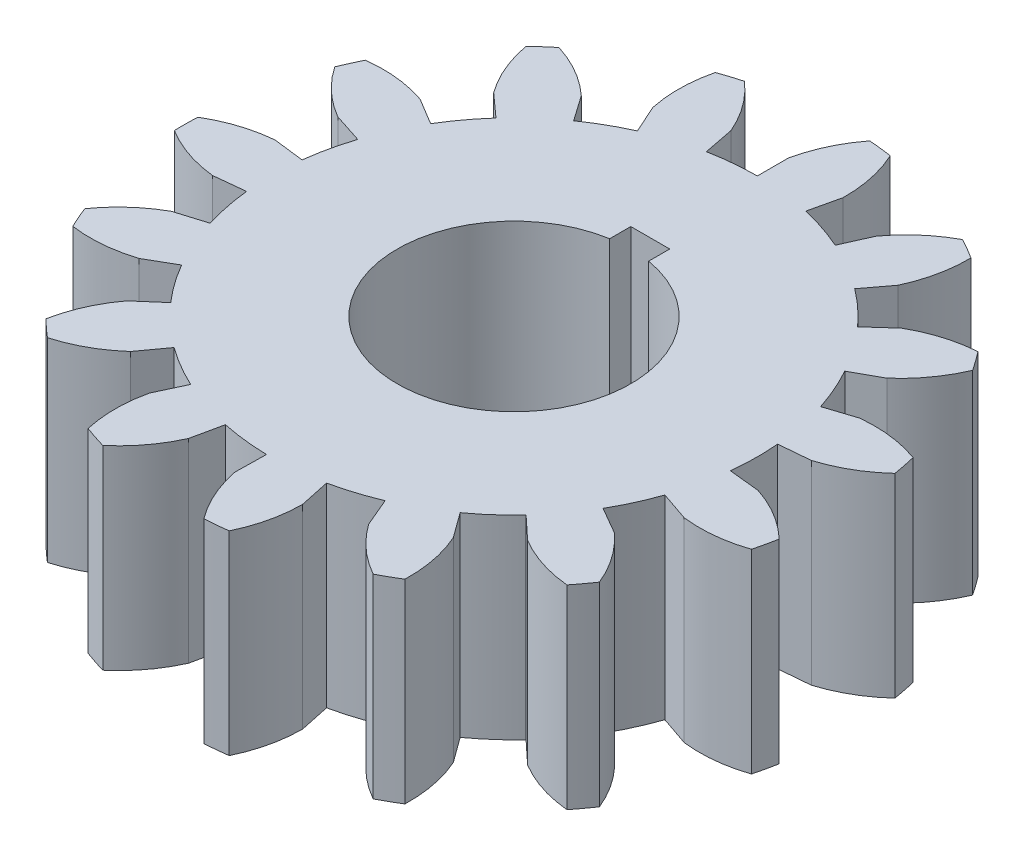
SolidWorks part; units mm, degrees
ref_plane "Front Plane" through (0, 0, 0) normal (0, 0, 1) x (1, 0, 0)
ref_plane "Top Plane" through (0, 0, 0) normal (0, 1, 0) x (1, 0, 0)
ref_plane "Right Plane" through (0, 0, 0) normal (1, 0, 0) x (0, 0, -1)
sketch "Sketch1" plane through (0, 0, 0) normal (0, 1, 0) x (1, 0, 0)
  circle A3 centre (0, 0) radius 6.25
  circle A4 centre (0, 0) radius 8.5
  circle A5 centre (0, 0) radius 7.5
  circle A6 centre (0, 0) radius 6.5
  circle A7 centre (0, 0) radius 7.0477
  dimension "pitch circle" = 15
  dimension "addendum circle" = 17
  dimension "root circle" = 12.5
  dimension "clearance circle" = 13
  dimension "base circle" = 14.0954
sketch "Sketch2" plane through (0, 0, 0) normal (0, 1, 0) x (1, 0, 0)
  line L0 (0, 0) -> (0, 7.0477)
  line L1 (0, 0) -> (3.5238, 6.1035) construction
  line L2 (0, 0) -> (6.1035, 3.5238) construction
  line L3 (0, 0) -> (7.0477, 0) construction
  line L4 (7.0477, 0) -> (7.0477, 11.0705) construction
  line L5 (6.1035, 3.5238) -> (2.4133, 9.9154) construction
  line L6 (3.5238, 6.1035) -> (0.3281, 7.9486) construction
  line L7 (0, 0) -> (3.0505, 6.8516)
  line L8 (0, 0) -> (1.5593, 7.3361) construction
  line L9 (0.8482, 7.4519) -> (0, 0) construction
  circle A0 centre (0, 0) radius 7.0477 construction
  circle A1 centre (0, 0) radius 7.5 construction
  arc A2 (1.5593, 7.3361) -> (0.1292, 7.4989) centre (0, 0) ccw
  spline S0 degree 3 poles (0, 7.0477) (0.62, 9.9338) (4.6694, 11.0743) (7.0477, 11.0705) knots 0 0 0 0 1 1 1 1
  spline S1 degree 3 poles (1.5838, 6.8674) (1.6283, 9.8191) (-2.0612, 11.8403) (-4.3795, 12.3712) knots 0 0 0 0 1 1 1 1
  point P11 (0, 0)
  point P21 (0, 0)
  point P22 (0, 0)
  point P23 (0, 0)
  point P24 (0, 0)
  point P25 (0, 0)
  point P26 (0, 0)
  dimension "Involute Control" = 90
  dimension "Base circle quarter circumference" = 11.0705
  dimension "D1" = 7.3803
  dimension "D2" = 3.6902
  dimension "pitch circle" = 24
  dimension "Involute array" = 4
sketch "Sketch3" plane through (0, 0, 0) normal (0, 1, 0) x (1, 0, 0)
  line L0 (1.5838, 6.8674) -> (1.4046, 6.0901)
  line L1 (0, 0) -> (0, 7.0477) construction
  line L3 (0, 6.25) -> (0, 7.0477)
  arc A1 (0.6639, 8.474) -> (0, 7.0477) centre (3.4619, 6.3041) ccw
  circle A2 centre (0, 0) radius 8.5 construction
  circle A3 centre (0, 0) radius 6.25 construction
  arc A7 (1.5838, 6.8674) -> (1.2575, 8.4065) centre (-1.9566, 6.9208) ccw
  arc A8 (1.4046, 6.0901) -> (0, 6.25) centre (0, 0) ccw
  arc A9 (1.2575, 8.4065) -> (0.6639, 8.474) centre (0, 0) ccw
  circle A10 centre (0, 0) radius 7.0477 construction
  spline S0 degree 3 poles (1.5838, 6.8674) (1.6283, 9.8191) (-2.0612, 11.8403) (-4.3795, 12.3712) knots 0 0 0 0 1 1 1 1 construction
  spline S1 degree 3 poles (0, 7.0477) (0.62, 9.9338) (4.6694, 11.0743) (7.0477, 11.0705) knots 0 0 0 0 1 1 1 1 construction
  point P5 (1.4736, 8.3713)
  point P6 (0, 0)
  point P15 (0.5842, 8.4799)
  point P16 (0, 0)
  point P22 (1.723, 6.0078)
  point P24 (1.3461, 6.1033)
  point P25 (0, 6.9566)
  point P28 (0.0787, 6.2495)
  point P29 (0, 0)
  point P32 (0, 0)
  point P33 (0, 0)
  point P34 (1.4046, 6.0901)
extrude "Boss-Extrude1" add sketch "Sketch3" along normal blind 5
sketch "Sketch5" plane through (0, 0, 0) normal (1, 0, 0) x (0, 0, -1)
  line L0 (0, 0) -> (0, 5.4709) construction
pattern_circular "CirPattern4" count 15 over 360 about axis through (0, 0, 0) along (0, 1, 0) reverse direction yes of bodies 101
sketch "Sketch6" plane through (0, 0, 0) normal (0, 1, 0) x (1, 0, 0)
  circle A0 centre (0, 0) radius 6.25 construction
  circle A1 centre (0, 0) radius 6.25
extrude "Boss-Extrude2" add sketch "Sketch6" along normal up to surface (5 mm away) up to face at (-2.1817, 5, -6.9167)
sketch "Sketch7" plane through (0, 5, 0) normal (0, 1, 0) x (1, 0, 0)
  line L1 (-0.5, 3.5) -> (0.5, 3.5)
  line L2 (-0.5, 3.5) -> (-0.5, 2.5)
  line L3 (-0.5, 2.5) -> (0.5, 2.5)
  line L4 (0.5, 3.5) -> (0.5, 2.5)
  line L5 (-0.5, 3.5) -> (0.5, 2.5) construction
  line L6 (-0.5, 2.5) -> (0.5, 3.5) construction
  circle A0 centre (0, 0) radius 3
  point P3 (0, 3)
  dimension "D1" = 6
  dimension "D2" = 1
extrude "Cut-Extrude1" cut sketch "Sketch7" against normal through all contours L2 A0 L4 L3 | L4 A0 L2 L3 | L4 L3 L2 L1 region at (0, 5, -2.7432) region at (0, 5, 0.048)
equation "\"Module\" = 1"
equation "\"Teeth number\" = 15"
equation "\"Pressure angle\"= 20deg"
equation "\"pitch circle@Sketch1\"= \"Module\" * \"Teeth number\""
equation "\"addendum circle@Sketch1\"= \"pitch circle@Sketch1\" + ( \"Module\" * 2 )"
equation "\"root circle@Sketch1\"= \"pitch circle@Sketch1\" - ( ( \"Module\" * 1.25 ) * 2 )"
equation "\"clearance circle@Sketch1\"= \"pitch circle@Sketch1\" - ( \"Module\" * 2 )"
equation "\"base circle@Sketch1\"= \"pitch circle@Sketch1\" * cos ( \"Pressure angle\" )"
equation "\"D1@Sketch2\"=\"Base circle quarter circumference@Sketch2\"/3*2"
equation "\"D2@Sketch2\"=\"Base circle quarter circumference@Sketch2\"/3"
equation "\"pitch circle@Sketch2\"=360/\"Teeth number\""
equation "\"D1@CirPattern4\"=\"Teeth number\""
equation "\"Base circle quarter circumference@Sketch2\"= \"base circle@Sketch1\" * pi / 4"
